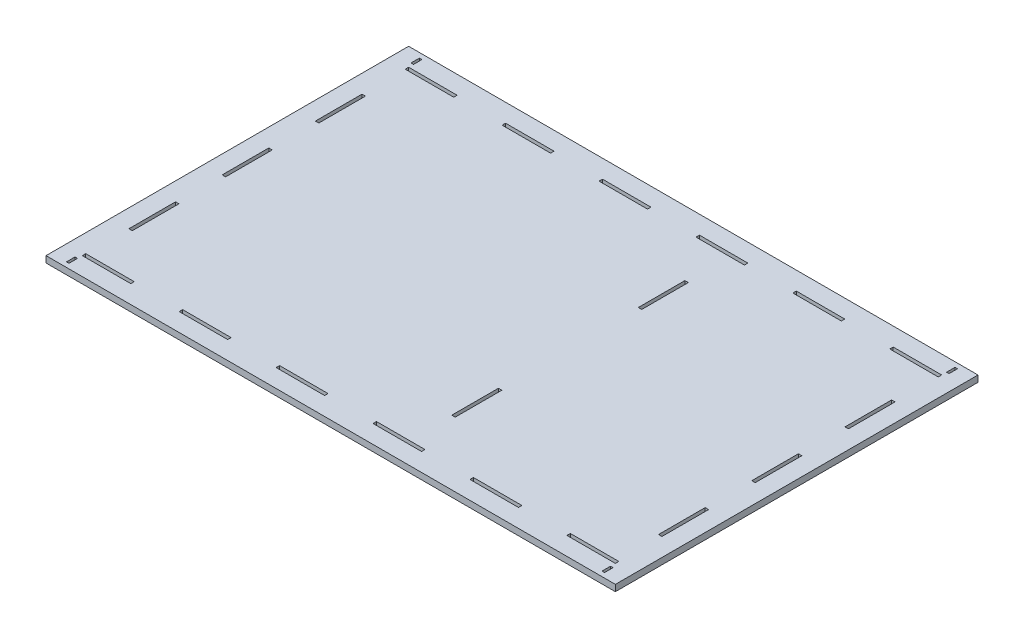
SolidWorks part; units mm, degrees
ref_plane "Front Plane" through (0, 0, 0) normal (0, 0, 1) x (1, 0, 0)
ref_plane "Top Plane" through (0, 0, 0) normal (0, 1, 0) x (1, 0, 0)
ref_plane "Right Plane" through (0, 0, 0) normal (1, 0, 0) x (0, 0, -1)
sketch "Sketch2" plane through (0, 0, 0) normal (0, 1, 0) x (1, 0, 0)
  line L0 (-230.0986, 0) -> (230.0986, 0) construction
  line L1 (-230.0986, 139.7) -> (230.0986, 139.7)
  line L2 (-230.0986, 139.7) -> (-230.0986, -139.7)
  line L3 (-230.0986, -139.7) -> (230.0986, -139.7)
  line L4 (230.0986, 139.7) -> (230.0986, -139.7)
  line L5 (0, 139.7) -> (0, -139.7) construction
  line L6 (-148.3337, -139.7) -> (-148.3337, -142.6972)
  line L15 (-230.0986, 142.6972) -> (-233.0958, 142.6972)
  line L16 (-230.0986, 142.6972) -> (-230.0986, 101.9266)
  line L17 (-230.0986, 101.9266) -> (-233.0958, 101.9266)
  line L18 (-233.0958, 142.6972) -> (-233.0958, 101.9266)
  line L19 (230.0986, 101.9266) -> (233.0958, 101.9266)
  line L20 (230.0986, 101.9266) -> (230.0986, 142.6972)
  line L21 (230.0986, 142.6972) -> (233.0958, 142.6972)
  line L22 (233.0958, 101.9266) -> (233.0958, 142.6972)
  line L23 (-190.7147, -139.7) -> (-233.0958, -139.7)
  line L24 (-190.7147, -139.7) -> (-190.7147, -142.6972)
  line L25 (-190.7147, -142.6972) -> (-233.0958, -142.6972)
  line L26 (-233.0958, -139.7) -> (-233.0958, -142.6972)
  line L27 (-233.0958, 142.6972) -> (-190.7147, 142.6972)
  line L28 (-233.0958, 142.6972) -> (-233.0958, 139.7)
  line L29 (-233.0958, 139.7) -> (-190.7147, 139.7)
  line L30 (-190.7147, 142.6972) -> (-190.7147, 139.7)
  line L31 (-148.3337, -139.7) -> (-190.7147, -139.7)
  line L32 (-190.7147, -139.7) -> (-190.7147, -142.6972)
  line L33 (-148.3337, -142.6972) -> (-190.7147, -142.6972)
  line L34 (-190.7147, 142.6972) -> (-190.7147, 139.7)
  line L35 (-190.7147, 142.6972) -> (-148.3337, 142.6972)
  line L36 (-148.3337, 142.6972) -> (-148.3337, 139.7)
  line L37 (-190.7147, 139.7) -> (-148.3337, 139.7)
  line L38 (-105.9526, -139.7) -> (-105.9526, -142.6972)
  line L39 (-105.9526, -139.7) -> (-148.3337, -139.7)
  line L40 (-148.3337, -139.7) -> (-148.3337, -142.6972)
  line L41 (-105.9526, -142.6972) -> (-148.3337, -142.6972)
  line L42 (-148.3337, 142.6972) -> (-148.3337, 139.7)
  line L43 (-148.3337, 142.6972) -> (-105.9526, 142.6972)
  line L44 (-105.9526, 142.6972) -> (-105.9526, 139.7)
  line L45 (-148.3337, 139.7) -> (-105.9526, 139.7)
  line L46 (-63.5716, -139.7) -> (-63.5716, -142.6972)
  line L47 (-63.5716, -139.7) -> (-105.9526, -139.7)
  line L48 (-105.9526, -139.7) -> (-105.9526, -142.6972)
  line L49 (-63.5716, -142.6972) -> (-105.9526, -142.6972)
  line L50 (-105.9526, 142.6972) -> (-105.9526, 139.7)
  line L51 (-105.9526, 142.6972) -> (-63.5716, 142.6972)
  line L52 (-63.5716, 142.6972) -> (-63.5716, 139.7)
  line L53 (-105.9526, 139.7) -> (-63.5716, 139.7)
  line L54 (-21.1905, -139.7) -> (-21.1905, -142.6972)
  line L55 (-21.1905, -139.7) -> (-63.5716, -139.7)
  line L56 (-63.5716, -139.7) -> (-63.5716, -142.6972)
  line L57 (-21.1905, -142.6972) -> (-63.5716, -142.6972)
  line L58 (-63.5716, 142.6972) -> (-63.5716, 139.7)
  line L59 (-63.5716, 142.6972) -> (-21.1905, 142.6972)
  line L60 (-21.1905, 142.6972) -> (-21.1905, 139.7)
  line L61 (-63.5716, 139.7) -> (-21.1905, 139.7)
  line L62 (21.1905, -139.7) -> (21.1905, -142.6972)
  line L63 (21.1905, -139.7) -> (-21.1905, -139.7)
  line L64 (-21.1905, -139.7) -> (-21.1905, -142.6972)
  line L65 (21.1905, -142.6972) -> (-21.1905, -142.6972)
  line L66 (-21.1905, 142.6972) -> (-21.1905, 139.7)
  line L67 (-21.1905, 142.6972) -> (21.1905, 142.6972)
  line L68 (21.1905, 142.6972) -> (21.1905, 139.7)
  line L69 (-21.1905, 139.7) -> (21.1905, 139.7)
  line L70 (63.5716, -139.7) -> (63.5716, -142.6972)
  line L71 (63.5716, -139.7) -> (21.1905, -139.7)
  line L72 (21.1905, -139.7) -> (21.1905, -142.6972)
  line L73 (63.5716, -142.6972) -> (21.1905, -142.6972)
  line L74 (21.1905, 142.6972) -> (21.1905, 139.7)
  line L75 (21.1905, 142.6972) -> (63.5716, 142.6972)
  line L76 (63.5716, 142.6972) -> (63.5716, 139.7)
  line L77 (21.1905, 139.7) -> (63.5716, 139.7)
  line L78 (105.9526, -139.7) -> (105.9526, -142.6972)
  line L79 (105.9526, -139.7) -> (63.5716, -139.7)
  line L80 (63.5716, -139.7) -> (63.5716, -142.6972)
  line L81 (105.9526, -142.6972) -> (63.5716, -142.6972)
  line L82 (63.5716, 142.6972) -> (63.5716, 139.7)
  line L83 (63.5716, 142.6972) -> (105.9526, 142.6972)
  line L84 (105.9526, 142.6972) -> (105.9526, 139.7)
  line L85 (63.5716, 139.7) -> (105.9526, 139.7)
  line L86 (148.3337, -139.7) -> (148.3337, -142.6972)
  line L87 (148.3337, -139.7) -> (105.9526, -139.7)
  line L88 (105.9526, -139.7) -> (105.9526, -142.6972)
  line L89 (148.3337, -142.6972) -> (105.9526, -142.6972)
  line L90 (105.9526, 142.6972) -> (105.9526, 139.7)
  line L91 (105.9526, 142.6972) -> (148.3337, 142.6972)
  line L92 (148.3337, 142.6972) -> (148.3337, 139.7)
  line L93 (105.9526, 139.7) -> (148.3337, 139.7)
  line L94 (190.7147, -139.7) -> (190.7147, -142.6972)
  line L95 (190.7147, -139.7) -> (148.3337, -139.7)
  line L96 (148.3337, -139.7) -> (148.3337, -142.6972)
  line L97 (190.7147, -142.6972) -> (148.3337, -142.6972)
  line L98 (148.3337, 142.6972) -> (148.3337, 139.7)
  line L99 (148.3337, 142.6972) -> (190.7147, 142.6972)
  line L100 (190.7147, 142.6972) -> (190.7147, 139.7)
  line L101 (148.3337, 139.7) -> (190.7147, 139.7)
  line L102 (233.0958, -139.7) -> (233.0958, -142.6972)
  line L103 (233.0958, -139.7) -> (190.7147, -139.7)
  line L104 (190.7147, -139.7) -> (190.7147, -142.6972)
  line L105 (233.0958, -142.6972) -> (190.7147, -142.6972)
  line L106 (190.7147, 142.6972) -> (190.7147, 139.7)
  line L107 (190.7147, 142.6972) -> (233.0958, 142.6972)
  line L108 (233.0958, 142.6972) -> (233.0958, 139.7)
  line L109 (190.7147, 139.7) -> (233.0958, 139.7)
  line L110 (-233.0958, 101.9266) -> (-233.0958, 61.1559)
  line L111 (-230.0986, 101.9266) -> (-230.0986, 61.1559)
  line L112 (-230.0986, 101.9266) -> (-233.0958, 101.9266)
  line L113 (-230.0986, 61.1559) -> (-233.0958, 61.1559)
  line L114 (230.0986, 61.1559) -> (230.0986, 101.9266)
  line L115 (230.0986, 61.1559) -> (233.0958, 61.1559)
  line L116 (233.0958, 61.1559) -> (233.0958, 101.9266)
  line L117 (230.0986, 101.9266) -> (233.0958, 101.9266)
  line L118 (-233.0958, 61.1559) -> (-233.0958, 20.3853)
  line L119 (-230.0986, 61.1559) -> (-230.0986, 20.3853)
  line L120 (-230.0986, 61.1559) -> (-233.0958, 61.1559)
  line L121 (-230.0986, 20.3853) -> (-233.0958, 20.3853)
  line L122 (230.0986, 20.3853) -> (230.0986, 61.1559)
  line L123 (230.0986, 20.3853) -> (233.0958, 20.3853)
  line L124 (233.0958, 20.3853) -> (233.0958, 61.1559)
  line L125 (230.0986, 61.1559) -> (233.0958, 61.1559)
  line L126 (-233.0958, 20.3853) -> (-233.0958, -20.3853)
  line L127 (-230.0986, 20.3853) -> (-230.0986, -20.3853)
  line L128 (-230.0986, 20.3853) -> (-233.0958, 20.3853)
  line L129 (-230.0986, -20.3853) -> (-233.0958, -20.3853)
  line L130 (230.0986, -20.3853) -> (230.0986, 20.3853)
  line L131 (230.0986, -20.3853) -> (233.0958, -20.3853)
  line L132 (233.0958, -20.3853) -> (233.0958, 20.3853)
  line L133 (230.0986, 20.3853) -> (233.0958, 20.3853)
  line L134 (-233.0958, -20.3853) -> (-233.0958, -61.1559)
  line L135 (-230.0986, -20.3853) -> (-230.0986, -61.1559)
  line L136 (-230.0986, -20.3853) -> (-233.0958, -20.3853)
  line L137 (-230.0986, -61.1559) -> (-233.0958, -61.1559)
  line L138 (230.0986, -61.1559) -> (230.0986, -20.3853)
  line L139 (230.0986, -61.1559) -> (233.0958, -61.1559)
  line L140 (233.0958, -61.1559) -> (233.0958, -20.3853)
  line L141 (230.0986, -20.3853) -> (233.0958, -20.3853)
  line L142 (-233.0958, -61.1559) -> (-233.0958, -101.9266)
  line L143 (-230.0986, -61.1559) -> (-230.0986, -101.9266)
  line L144 (-230.0986, -61.1559) -> (-233.0958, -61.1559)
  line L145 (-230.0986, -101.9266) -> (-233.0958, -101.9266)
  line L146 (230.0986, -101.9266) -> (230.0986, -61.1559)
  line L147 (230.0986, -101.9266) -> (233.0958, -101.9266)
  line L148 (233.0958, -101.9266) -> (233.0958, -61.1559)
  line L149 (230.0986, -61.1559) -> (233.0958, -61.1559)
  line L150 (-233.0958, -101.9266) -> (-233.0958, -142.6972)
  line L151 (-230.0986, -101.9266) -> (-230.0986, -142.6972)
  line L152 (-230.0986, -101.9266) -> (-233.0958, -101.9266)
  line L153 (-230.0986, -142.6972) -> (-233.0958, -142.6972)
  line L154 (230.0986, -142.6972) -> (230.0986, -101.9266)
  line L155 (230.0986, -142.6972) -> (233.0958, -142.6972)
  line L156 (233.0958, -142.6972) -> (233.0958, -101.9266)
  line L157 (230.0986, -101.9266) -> (233.0958, -101.9266)
  point P9 (0, 0)
  dimension "D1" = 279.4
  dimension "D2" = 460.1972
  dimension "D3" = 466.1916
  dimension "D4" = 285.3944
  dimension "D6" = 42.3811
  dimension "D8" = 40.7706
  dimension "D5" = 11
  dimension "D7" = 7
extrude "Boss-Extrude1" add sketch "Sketch2" along normal blind 5.588 contours L4 L1 L2 L3 | L36 L35 L30 L1 | L29 L18 L17 L2 | L121 L2 L113 L118 | L137 L2 L129 L134 | L52 L51 L44 L1 | L68 L67 L60 L1 | L84 L83 L76 L1 | L100 L99 L92 L1 | L97 L94 L3 L86 | L81 L78 L3 L70 | L65 L62 L3 L54 | L49 L46 L3 L38 | L33 L6 L3 L24 | L145 L150 L23 L2 | L103 L156 L147 L4 | L139 L140 L131 L4 | L123 L124 L115 L4 | L109 L4 L19 L22 region at (0, 0, 0) region at (-231.5972, 0, -120.8133) region at (-169.5242, 0, -141.1986) region at (-231.5972, 0, -40.7706) region at (-84.7621, 0, -141.1986) region at (-231.5972, 0, 40.7706) region at (0, 0, -141.1986) region at (-231.5972, 0, 120.8133) region at (84.7621, 0, -141.1986) region at (-169.5242, 0, 141.1986) region at (169.5242, 0, -141.1986) region at (-84.7621, 0, 141.1986) region at (231.5972, 0, -120.8133) region at (0, 0, 141.1986) region at (231.5972, 0, -40.7706) region at (84.7621, 0, 141.1986) region at (231.5972, 0, 40.7706) region at (169.5242, 0, 141.1986) region at (231.5972, 0, 120.8133)
sketch "Sketch3" plane through (0, 5.588, 0) normal (0, 1, 0) x (1, 0, 0)
  line L0 (50.8, -61.1559) -> (50.8, 61.1559) construction
  line L1 (49.3014, 101.9266) -> (52.2986, 101.9266)
  line L2 (49.3014, 101.9266) -> (49.3014, 61.1559)
  line L3 (49.3014, 61.1559) -> (52.2986, 61.1559)
  line L4 (52.2986, 101.9266) -> (52.2986, 61.1559)
  line L5 (49.3014, -101.9266) -> (52.2986, -101.9266)
  line L6 (49.3014, -101.9266) -> (49.3014, -61.1559)
  line L7 (49.3014, -61.1559) -> (52.2986, -61.1559)
  line L8 (52.2986, -101.9266) -> (52.2986, -61.1559)
  line L9 (0, 0) -> (50.8, 0) construction
  line L10 (-230.0986, 101.9266) -> (-233.0958, 101.9266) construction
  line L12 (52.2986, -101.9266) -> (49.3014, -101.9266)
  line L13 (52.2986, -101.9266) -> (52.2986, -142.6972)
  line L14 (52.2986, -142.6972) -> (49.3014, -142.6972)
  line L15 (49.3014, -101.9266) -> (49.3014, -142.6972)
  line L17 (52.2986, 101.9266) -> (49.3014, 101.9266)
  line L18 (52.2986, 101.9266) -> (52.2986, 142.6972)
  line L19 (52.2986, 142.6972) -> (49.3014, 142.6972)
  line L20 (49.3014, 101.9266) -> (49.3014, 142.6972)
  line L21 (-230.0986, -61.1559) -> (-230.0986, -101.9266) construction
  line L22 (-230.0986, 101.9266) -> (-230.0986, 61.1559) construction
  dimension "D1" = 279.4
extrude "Cut-Extrude1" cut sketch "Sketch3" against normal through all contours L5 L8 L7 L6 | L4 L1 L2 L3 region at (50.8, 5.588, -81.5413) region at (50.8, 5.588, 81.5413)
sketch "Sketch4" plane through (0, 5.588, 0) normal (0, 1, 0) x (1, 0, 0)
  line L0 (-233.0958, 139.7) -> (-233.0958, 101.9266) construction
  line L1 (-233.0958, 158.5722) -> (-248.9708, 158.5722)
  line L2 (-233.0958, 158.5722) -> (-233.0958, -158.5722)
  line L3 (-233.0958, -158.5722) -> (-248.9708, -158.5722)
  line L4 (-248.9708, 158.5722) -> (-248.9708, -158.5722)
  line L5 (148.3337, 142.6972) -> (190.7147, 142.6972) construction
  line L6 (-233.0958, 158.5722) -> (233.0958, 158.5722)
  line L7 (-233.0958, 158.5722) -> (-233.0958, 142.6972)
  line L8 (-233.0958, 142.6972) -> (233.0958, 142.6972)
  line L9 (233.0958, 158.5722) -> (233.0958, 142.6972)
  line L10 (-228.0134, -142.6972) -> (-228.0134, -158.5722) construction
  line L15 (190.7147, -142.6972) -> (148.3337, -142.6972) construction
  line L16 (-233.0958, -158.5722) -> (233.0958, -158.5722)
  line L17 (-233.0958, -158.5722) -> (-233.0958, -142.6972)
  line L18 (-233.0958, -142.6972) -> (233.0958, -142.6972)
  line L19 (233.0958, -158.5722) -> (233.0958, -142.6972)
  line L20 (233.0958, 101.9266) -> (233.0958, 139.7) construction
  line L21 (233.0958, 158.5722) -> (248.9708, 158.5722)
  line L22 (233.0958, 158.5722) -> (233.0958, -158.5722)
  line L23 (233.0958, -158.5722) -> (248.9708, -158.5722)
  line L24 (248.9708, 158.5722) -> (248.9708, -158.5722)
  line L25 (-248.9708, 0) -> (248.9708, 0) construction
  line L26 (-228.0134, -150.6347) -> (-235.2958, -150.6347) construction
  line L27 (-235.2958, -146.92) -> (-233.0958, -146.92)
  line L28 (-235.2958, -146.92) -> (-235.2958, -154.3494)
  line L29 (-235.2958, -154.3494) -> (-233.0958, -154.3494)
  line L30 (-233.0958, -146.92) -> (-233.0958, -154.3494)
  line L32 (-234.1958, 146.92) -> (-234.1958, -146.92) construction
  line L33 (-233.0958, 154.3494) -> (-235.2958, 154.3494)
  line L34 (-233.0958, 154.3494) -> (-233.0958, 146.92)
  line L35 (-233.0958, 146.92) -> (-235.2958, 146.92)
  line L36 (-235.2958, 154.3494) -> (-235.2958, 146.92)
  line L37 (0, -3.0734) -> (0, 3.0734) construction
  line L38 (233.0958, 146.92) -> (235.2958, 146.92)
  line L39 (235.2958, 154.3494) -> (235.2958, 146.92)
  line L40 (233.0958, 154.3494) -> (235.2958, 154.3494)
  line L41 (233.0958, 154.3494) -> (233.0958, 146.92)
  line L42 (235.2958, -154.3494) -> (233.0958, -154.3494)
  line L43 (233.0958, -146.92) -> (233.0958, -154.3494)
  line L44 (235.2958, -146.92) -> (233.0958, -146.92)
  line L45 (235.2958, -146.92) -> (235.2958, -154.3494)
  point P12 (0, 0)
  point P39 (-234.1958, 0)
  dimension "D1" = 15.875
  dimension "D2" = 15.875
  dimension "D3" = 2.2
  dimension "D4" = 7.4295
extrude "Boss-Extrude2" add sketch "Sketch4" against normal up to surface (5.588 mm away) contours L9 L6 L2 L8 | L4 L25 L2 L1 | L16 L19 L18 L2 | L25 L22 L19 L23 L24 region at (-241.078, 5.588, 0) region at (0, 5.588, -150.6347) region at (241.078, 5.588, 0) region at (0, 5.588, 150.6347) up to face at (50.8, 0, 81.5413)
equation "\"wallthickness\"= .118in"
equation "\"floorThickness\"= .220in"
equation "\"D2@Sketch2\"=11+7+\"wallthickness\""
equation "\"D3@Sketch2\"=\"wallthickness\"*2+\"D2@Sketch2\""
equation "\"D4@Sketch2\"=\"wallthickness\"*2+\"D1@Sketch2\""
equation "\"D6@Sketch2\"=\"D3@Sketch2\"/\"D5@Sketch2\""
equation "\"D8@Sketch2\"=\"D4@Sketch2\"/\"D7@Sketch2\""
equation "\"D1@Boss-Extrude1\"=\"floorThickness\""
equation "\"D2@Sketch4\"=\"D1@Sketch4\""
